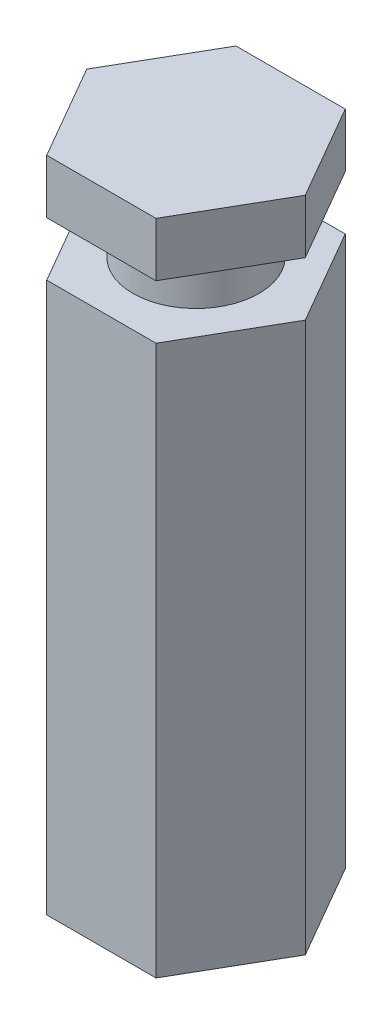
SolidWorks part; units mm, degrees
ref_plane "Front Plane" through (0, 0, 0) normal (0, 0, 1) x (1, 0, 0)
ref_plane "Top Plane" through (0, 0, 0) normal (0, 1, 0) x (1, 0, 0)
ref_plane "Right Plane" through (0, 0, 0) normal (1, 0, 0) x (0, 0, -1)
sketch "Sketch1" plane through (0, 0, 0) normal (0, 1, 0) x (1, 0, 0)
  line L6 (-55, 0) -> (55, 0) construction
  line L7 (12.1244, 0) -> (6.0622, 10.5)
  line L8 (6.0622, 10.5) -> (-6.0622, 10.5)
  line L9 (-6.0622, 10.5) -> (-12.1244, 0)
  line L10 (-12.1244, 0) -> (-6.0622, -10.5)
  line L11 (-6.0622, -10.5) -> (6.0622, -10.5)
  line L12 (6.0622, -10.5) -> (12.1244, 0)
  circle A1 centre (0, 0) radius 7
  circle A2 centre (0, 0) radius 10.5 construction
  point P1 (0, 0)
  dimension "D1" = 21
  dimension "D2" = 14
extrude "Boss-Extrude1" add sketch "Sketch1" along normal blind 61 contours L11 L12 L7 L8 L9 L10 A1 | A1 region at (8.8155, 0, 5.0896) region at (0, 0, 0)
extrude "Boss-Extrude2" add sketch "Sketch1<3>" along normal blind 67 contours A1 region at (0, 0, 0)
sketch "Sketch1<3>" plane through (0, 0, 0) normal (0, 1, 0) x (1, 0, 0) same geometry as "Sketch1"
extrude "Boss-Extrude3" add sketch "Sketch1<4>" along normal blind 6 from surface contours L11 L12 L7 L8 L9 L10 A1 | A1 region at (8.8155, 0, 5.0896) region at (0, 0, 0) starting at face at (0, 67, 7)
sketch "Sketch1<4>" plane through (0, 0, 0) normal (0, 1, 0) x (1, 0, 0) same geometry as "Sketch1"
